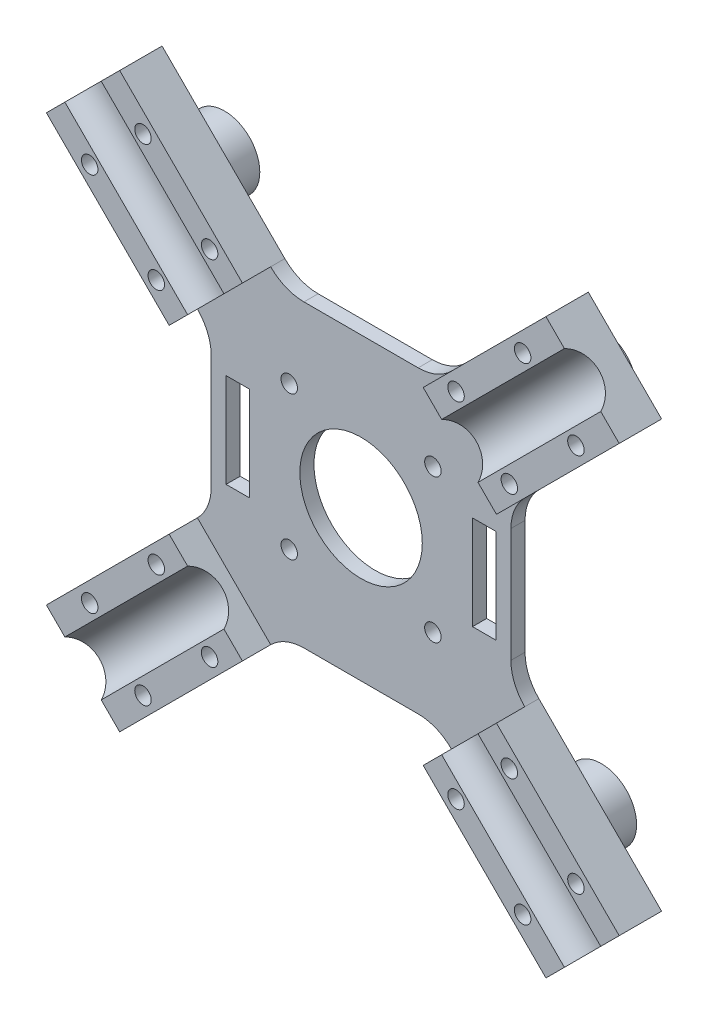
SolidWorks part; units mm, degrees
ref_plane "Front Plane" through (0, 0, 0) normal (0, 0, 1) x (1, 0, 0)
ref_plane "Top Plane" through (0, 0, 0) normal (0, 1, 0) x (1, 0, 0)
ref_plane "Right Plane" through (0, 0, 0) normal (1, 0, 0) x (0, 0, -1)
sketch "Sketch1" plane through (0, 0, 0) normal (0, 0, 1) x (1, 0, 0)
  line L0 (-15.25, 15.25) -> (15.25, 15.25) construction
  line L5 (-31.8198, -31.8198) -> (-45.9619, -45.9619) construction
  line L6 (0, 0) -> (0, 35.81) construction
  line L13 (0, 0) -> (0, -35) construction
  line L14 (-31.8198, -31.8198) -> (-26.163, -37.4767) construction
  line L15 (24.0416, 39.598) -> (19.1924, 34.7487)
  line L16 (0, 0) -> (-73.0115, -73.0115) construction
  line L22 (-39.598, -24.0416) -> (-60.8112, -45.2548)
  line L24 (-40.3051, -51.6188) -> (-51.6188, -40.3051) construction
  line L25 (-31.8198, -31.8198) -> (-37.4767, -26.163) construction
  line L26 (39.598, 24.0416) -> (34.7487, 19.1924)
  line L27 (-24.0416, -39.598) -> (-45.2548, -60.8112)
  line L28 (-45.2548, -60.8112) -> (-60.8112, -45.2548)
  line L29 (-39.598, -24.0416) -> (-34.7487, -19.1924)
  line L31 (51.6188, 40.3051) -> (40.3051, 51.6188) construction
  line L32 (0, 0) -> (-72.4223, 72.4223) construction
  line L35 (-24.0416, -39.598) -> (-19.1924, -34.7487)
  line L39 (0, 0) -> (77.7251, -77.7251) construction
  line L40 (-20, 25) -> (20, 25) construction
  line L41 (31.8198, 31.8198) -> (37.4767, 26.163) construction
  line L42 (20, 25) -> (20, -25) construction
  line L43 (20, -25) -> (-20, -25) construction
  line L44 (-20, 25) -> (-20, -25) construction
  line L45 (31.8198, 31.8198) -> (26.163, 37.4767) construction
  line L46 (31.8198, 31.8198) -> (45.9619, 45.9619) construction
  line L48 (24.0416, 39.598) -> (45.2548, 60.8112)
  line L49 (60.8112, 45.2548) -> (45.2548, 60.8112)
  line L51 (0, 0) -> (31.8198, 31.8198) construction
  line L57 (31.8198, 31.8198) -> (-31.8198, 31.8198) construction
  line L58 (39.598, 24.0416) -> (60.8112, 45.2548)
  line L59 (0, 0) -> (84.5807, 0) construction
  line L60 (31.8198, -31.8198) -> (45.9619, -45.9619) construction
  line L62 (31.8198, -31.8198) -> (26.163, -37.4767) construction
  line L63 (31.8198, -31.8198) -> (37.4767, -26.163) construction
  line L64 (51.6188, -40.3051) -> (40.3051, -51.6188) construction
  line L65 (39.598, -24.0416) -> (60.8112, -45.2548)
  line L68 (-15.25, -15.25) -> (15.25, 15.25) construction
  line L69 (-15.25, 15.25) -> (15.25, -15.25) construction
  line L70 (15.25, 15.25) -> (15.25, -15.25) construction
  line L71 (15.25, -15.25) -> (-15.25, -15.25) construction
  line L72 (-15.25, -15.25) -> (-15.25, 15.25) construction
  line L73 (-15.25, 15.25) -> (-50.1815, 15.25) construction
  line L74 (15.25, 15.25) -> (50.1815, 15.25) construction
  line L75 (15.25, -15.25) -> (50.1815, -15.25) construction
  line L76 (-15.25, -15.25) -> (-50.1815, -15.25) construction
  line L77 (-31.8198, 31.8198) -> (-31.8198, -31.8198) construction
  line L82 (-31.8198, -31.8198) -> (31.8198, -31.8198) construction
  line L83 (31.8198, -31.8198) -> (31.8198, 31.8198) construction
  line L84 (12.1213, 31.8198) -> (-12.1213, 31.8198)
  line L89 (-31.8198, 15.25) -> (-31.8198, -12.1213)
  line L90 (-12.1213, -31.8198) -> (12.1213, -31.8198)
  line L95 (31.8198, -15.25) -> (31.8198, 15.25)
  line L96 (60.8112, -45.2548) -> (45.2548, -60.8112)
  line L102 (24.0416, -39.598) -> (45.2548, -60.8112)
  line L103 (39.598, -24.0416) -> (34.7487, -19.1924)
  line L104 (24.0416, -39.598) -> (19.1924, -34.7487)
  line L105 (-31.8198, 31.8198) -> (-37.4767, 26.163) construction
  line L106 (-40.3051, 51.6188) -> (-51.6188, 40.3051) construction
  line L107 (-31.8198, 31.8198) -> (-26.163, 37.4767) construction
  line L108 (-31.8198, 31.8198) -> (-45.9619, 45.9619) construction
  line L109 (-24.0416, 39.598) -> (-19.1924, 34.7487)
  line L110 (-39.598, 24.0416) -> (-34.7487, 19.1924)
  line L111 (-45.2548, 60.8112) -> (-60.8112, 45.2548)
  line L112 (-24.0416, 39.598) -> (-45.2548, 60.8112)
  line L113 (-39.598, 24.0416) -> (-60.8112, 45.2548)
  line L116 (31.8198, 31.8198) -> (38.8909, 38.8909) construction
  line L117 (-23.663, -10) -> (-28.663, -10)
  line L118 (23.663, -10) -> (28.663, -10)
  line L119 (23.663, -10) -> (23.663, 10)
  line L122 (23.663, 10) -> (28.663, 10)
  line L123 (28.663, -10) -> (28.663, 10)
  line L124 (0, 0) -> (66.0317, 66.0317) construction
  line L125 (23.663, -10) -> (28.663, 10) construction
  line L126 (23.663, 10) -> (28.663, -10) construction
  line L127 (-28.663, -10) -> (-28.663, 10)
  line L128 (-23.663, -10) -> (-23.663, 10)
  line L129 (-23.663, 10) -> (-28.663, 10)
  circle A0 centre (15.25, 15.25) radius 1.75
  circle A1 centre (-15.25, 15.25) radius 1.75
  circle A2 centre (15.25, -15.25) radius 1.75
  circle A3 centre (-15.25, -15.25) radius 1.75
  circle A21 centre (0, 0) radius 13
  circle A22 centre (-37.4767, -26.163) radius 1.75
  circle A23 centre (-26.163, -37.4767) radius 1.75
  circle A24 centre (-40.3051, -51.6188) radius 1.75
  circle A25 centre (-51.6188, -40.3051) radius 1.75
  arc A26 (-31.8198, -12.1213) -> (-34.7487, -19.1924) centre (-41.8198, -12.1213) cw
  arc A27 (-12.1213, -31.8198) -> (-19.1924, -34.7487) centre (-12.1213, -41.8198) ccw
  arc A28 (12.1213, 31.8198) -> (19.1924, 34.7487) centre (12.1213, 41.8198) ccw
  arc A29 (31.8198, 12.1213) -> (34.7487, 19.1924) centre (41.8198, 12.1213) cw
  circle A30 centre (26.163, 37.4767) radius 1.75
  circle A31 centre (37.4767, 26.163) radius 1.75
  circle A32 centre (51.6188, 40.3051) radius 1.75
  circle A33 centre (40.3051, 51.6188) radius 1.75
  arc A34 (31.8198, -12.1213) -> (34.7487, -19.1924) centre (41.8198, -12.1213) ccw
  circle A35 centre (40.3051, -51.6188) radius 1.75
  circle A36 centre (51.6188, -40.3051) radius 1.75
  circle A37 centre (37.4767, -26.163) radius 1.75
  circle A38 centre (26.163, -37.4767) radius 1.75
  arc A39 (12.1213, -31.8198) -> (19.1924, -34.7487) centre (12.1213, -41.8198) cw
  arc A40 (-12.1213, 31.8198) -> (-19.1924, 34.7487) centre (-12.1213, 41.8198) cw
  arc A41 (-31.8198, 12.1213) -> (-34.7487, 19.1924) centre (-41.8198, 12.1213) ccw
  circle A42 centre (-51.6188, 40.3051) radius 1.75
  circle A43 centre (-40.3051, 51.6188) radius 1.75
  circle A44 centre (-26.163, 37.4767) radius 1.75
  circle A45 centre (-37.4767, 26.163) radius 1.75
  point P0 (0, 0)
  point P106 (26.163, 0)
  dimension "D1" = 10
extrude "Boss-Extrude1" add sketch "Sketch1" along normal blind 3 contours A41 L89 A26 L29 L22 L28 L27 L35 A27 L90 A39 L104 L102 L96 L65 L103 A34 L95 A29 L26 L58 L49 L48 L15 A28 L84 A40 L109 L112 L111 L113 L110 A44 A42 A38 A37 A36 A35 region at (35.8645, 48.9884, 0)
sketch "Sketch2" plane through (0, 0, 0) normal (0, 0, 1) x (1, 0, 0)
sketch "Sketch3" plane through (0, 0, 0) normal (0, 0, 1) x (1, 0, 0)
  line L0 (-47.78, 32.2236) -> (-32.2236, 47.78) construction
  line L1 (-34.7487, 19.1924) -> (-60.8112, 45.2548) construction
  line L2 (-45.2548, 60.8112) -> (-19.1924, 34.7487) construction
  line L3 (-53.033, 53.033) -> (-25.6834, 25.6834) construction
  line L4 (-45.2548, 60.8112) -> (-60.8112, 45.2548) construction
  line L5 (55, 0) -> (-55, 0) construction
  line L6 (0, -55) -> (0, 55) construction
  circle A0 centre (-40.0018, 40.0018) radius 4.75
  circle A1 centre (-40.0018, 40.0018) radius 7.5
  circle A2 centre (-40.0018, -40.0018) radius 7.5
  circle A3 centre (-40.0018, -40.0018) radius 4.75
  circle A4 centre (40.0018, -40.0018) radius 4.75
  circle A5 centre (40.0018, -40.0018) radius 7.5
  circle A6 centre (40.0018, 40.0018) radius 7.5
  circle A7 centre (40.0018, 40.0018) radius 4.75
extrude "Boss-Extrude2" add sketch "Sketch3" against normal blind 8
ref_plane "Plane1" through (0, 0, 3) normal (0, 0, 1) x (1, 0, 0)
sketch "Sketch7" plane through (0, 0, 3) normal (0, 0, 1) x (1, 0, 0)
  line L0 (-34.7487, 19.1924) -> (-19.1924, 34.7487)
  line L1 (-19.1924, 34.7487) -> (-45.2548, 60.8112)
  line L2 (-45.2548, 60.8112) -> (-60.8112, 45.2548)
  line L3 (-60.8112, 45.2548) -> (-34.7487, 19.1924)
  line L4 (6.05, 0) -> (-6.05, 0) construction
  line L5 (-60.8112, -45.2548) -> (-34.7487, -19.1924)
  line L6 (-45.2548, -60.8112) -> (-60.8112, -45.2548)
  line L7 (-19.1924, -34.7487) -> (-45.2548, -60.8112)
  line L8 (-34.7487, -19.1924) -> (-19.1924, -34.7487)
  line L9 (0, -6.05) -> (0, 6.05) construction
  line L10 (34.7487, -19.1924) -> (19.1924, -34.7487)
  line L11 (19.1924, -34.7487) -> (45.2548, -60.8112)
  line L12 (45.2548, -60.8112) -> (60.8112, -45.2548)
  line L13 (60.8112, -45.2548) -> (34.7487, -19.1924)
  line L14 (60.8112, 45.2548) -> (34.7487, 19.1924)
  line L15 (45.2548, 60.8112) -> (60.8112, 45.2548)
  line L16 (19.1924, 34.7487) -> (45.2548, 60.8112)
  line L17 (34.7487, 19.1924) -> (19.1924, 34.7487)
extrude "Boss-Extrude4" add sketch "Sketch7" along normal blind 6
extrude "Cut-Extrude3" cut sketch "Sketch1<5>" along normal blind 21 and the other way blind 10 contours A42 | A43 | A45 | A44 | A22 | A25 | A24 | A23 | A35 | A38 | A37 | A36 | A31 | A30 | A33 | A32
sketch "Sketch1<5>" plane through (0, 0, 0) normal (0, 0, 1) x (1, 0, 0) same geometry as "Sketch1"
ref_plane "Plane2" through (-53.033, 53.033, 0) normal (-0.7071, 0.7071, 0) x (0, 0, 1)
sketch "Sketch10" plane through (-53.033, 53.033, 0) normal (-0.7071, 0.7071, 0) x (0, 0, 1)
  line L0 (0, 0) -> (3, 0) construction
  line L1 (0, 11) -> (0, -11) construction
  line L2 (3, -82.5811) -> (3, 82.5811) construction
  line L3 (3, 0) -> (11.5, 0) construction
  circle A1 centre (11.5, 0) radius 6
extrude "Cut-Extrude4" cut sketch "Sketch10" against normal up to surface (150 mm away) up to face at (53.033, -53.033, 4.5)
ref_plane "Plane3" through (53.033, 53.033, 0) normal (0.7071, 0.7071, 0) x (0.7071, -0.7071, 0)
sketch "Sketch11" plane through (53.033, 53.033, 0) normal (0.7071, 0.7071, 0) x (0.7071, -0.7071, 0)
  line L0 (0, 0) -> (0, -3) construction
  line L1 (-82.5811, -3) -> (82.5811, -3) construction
  line L2 (0, -3) -> (0, -11.5) construction
  circle A0 centre (0, -11.5) radius 6
extrude "Cut-Extrude5" cut sketch "Sketch11" against normal up to surface (150 mm away) up to face at (-53.033, -53.033, 4.5)
